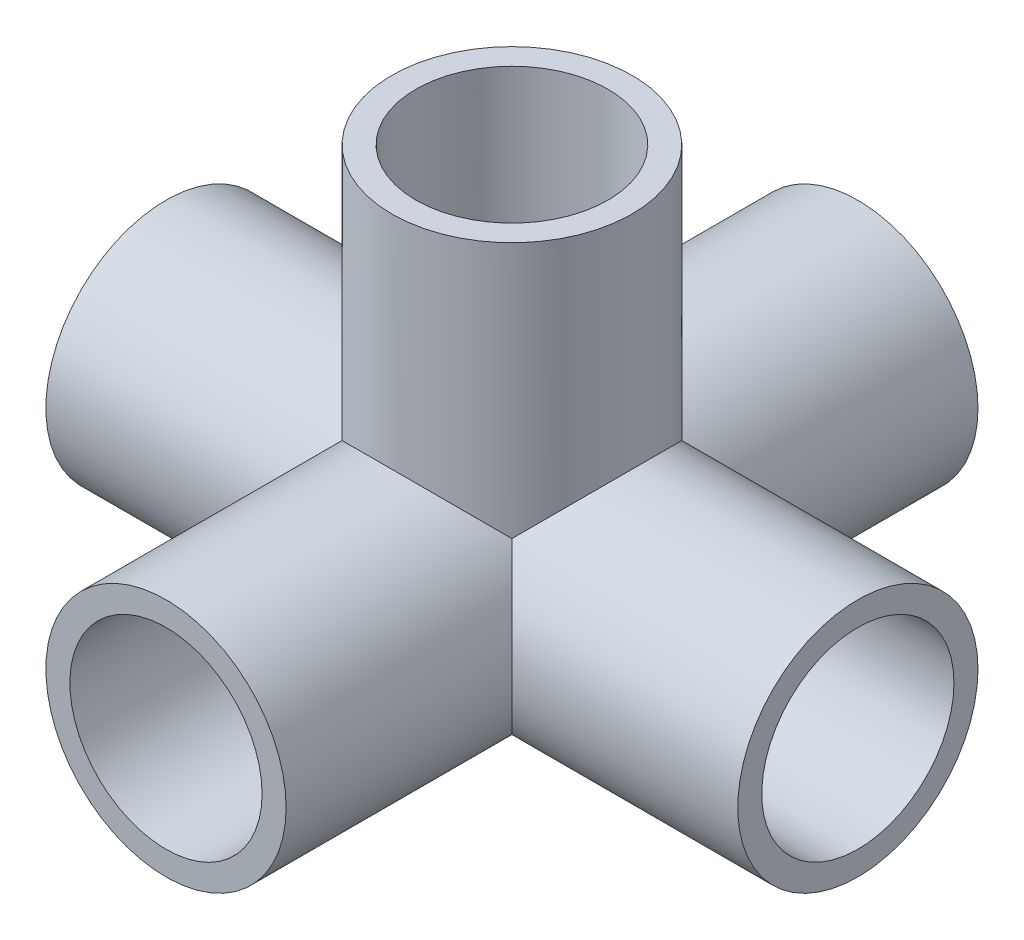
SolidWorks part; units mm, degrees
ref_plane "前视基准面" through (0, 0, 0) normal (0, 0, 1) x (1, 0, 0)
ref_plane "上视基准面" through (0, 0, 0) normal (0, 1, 0) x (1, 0, 0)
ref_plane "右视基准面" through (0, 0, 0) normal (1, 0, 0) x (0, 0, -1)
sketch "草图1" plane through (0, 0, 0) normal (1, 0, 0) x (0, 0, -1)
  circle A1 centre (0, 0) radius 10
  dimension "D2" = 20
extrude "凸台-拉伸1" add sketch "草图1" along normal mid plane 72
sketch "草图2" plane through (0, 0, 0) normal (0, 1, 0) x (1, 0, 0)
  circle A1 centre (0, 0) radius 10
  dimension "D2" = 20
extrude "凸台-拉伸2" add sketch "草图2" along normal blind 35.5
sketch "草图3" plane through (0, 0, 0) normal (0, 0, 1) x (1, 0, 0)
  circle A1 centre (0, 0) radius 10
  dimension "D2" = 20
extrude "凸台-拉伸3" add sketch "草图3" along normal mid plane 72
shell "抽壳1" thickness 2.5 removed face at (-36, 0, -10) removed face at (36, 0, -10) removed face at (10, 0, 36) removed face at (0, 35.5, 10) removed face at (10, 0, -36) outward yes
